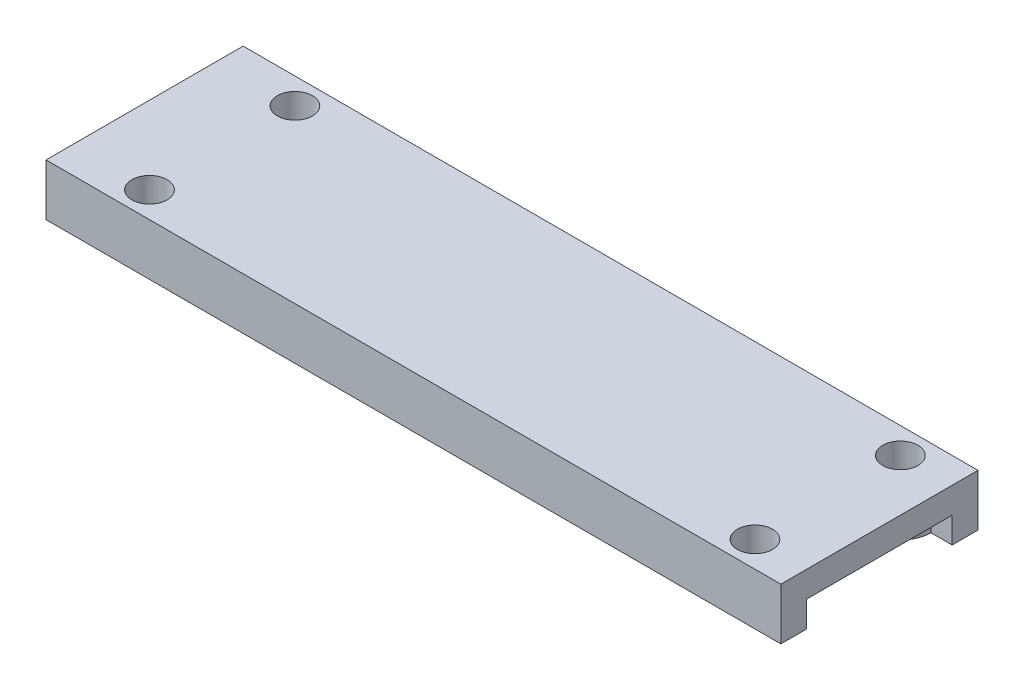
SolidWorks part; units mm, degrees
material "1060 Alloy"
ref_plane "Front Plane" through (0, 0, 0) normal (0, 0, 1) x (1, 0, 0)
ref_plane "Top Plane" through (0, 0, 0) normal (0, 1, 0) x (1, 0, 0)
ref_plane "Right Plane" through (0, 0, 0) normal (1, 0, 0) x (0, 0, -1)
sketch "Sketch1" plane through (0, 0, 0) normal (0, 1, 0) x (1, 0, 0)
  line L1 (-71, -19.05) -> (71, -19.05)
  line L2 (-71, -19.05) -> (-71, 19.05)
  line L3 (-71, 19.05) -> (71, 19.05)
  line L4 (71, -19.05) -> (71, 19.05)
  line L5 (-71, -19.05) -> (71, 19.05) construction
  line L6 (-71, 19.05) -> (71, -19.05) construction
  point P0 (0, 0)
  dimension "D1" = 142
  dimension "D2" = 38.1
extrude "Boss-Extrude1" add sketch "Sketch1" along normal mid plane 10
sketch "Sketch2" plane through (0, 0, 0) normal (1, 0, 0) x (0, 0, -1)
  line L0 (-14.05, 0) -> (14.05, 0)
  line L1 (14.05, 0) -> (14.05, -5)
  line L2 (-19.05, -5) -> (19.05, -5) construction
  line L3 (14.05, -5) -> (-14.05, -5)
  line L4 (-14.05, -5) -> (-14.05, 0)
  line L5 (-19.05, 5) -> (-19.05, -5) construction
  dimension "D1" = 5
extrude "Cut-Extrude1" cut sketch "Sketch2" against normal through all both and the other way through all
hole_wizard "Tap Drill for M8x1.25 Tap1" positions "Sketch4" profile "Sketch3" hole size "M8x1.25" standard "ANSI Metric"
sketch "Sketch4" plane through (0, 5, 0) normal (0, 1, 0) x (1, 0, 0)
  line L0 (71, 19.05) -> (-71, 19.05) construction
  line L2 (-71, 19.05) -> (-71, -19.05) construction
  line L3 (-71, -19.05) -> (71, -19.05) construction
  line L4 (71, -19.05) -> (71, 19.05) construction
  point P0 (-56, 14.05)
  point P2 (61, 14.05)
  point P4 (61, -14.05)
  point P6 (-56, -14.05)
  dimension "D1" = 5
  dimension "D2" = 15
  dimension "D3" = 15
  dimension "D4" = 5
  dimension "D5" = 10
  dimension "D6" = 10
  dimension "D7" = 5
  dimension "D8" = 5
sketch "Sketch3" plane through (-56, 5, -14.05) normal (1, 0, 0) x (0, 0, 1)
  line L0 (0, 0) -> (0, 14.0429)
  line L1 (0, 14.0429) -> (3.4, 12)
  line L2 (3.4, 12) -> (3.4, 0)
  line L5 (3.4, 0) -> (0, 0)
  line L10 (0, 14.0429) -> (-3.4, 12) construction
  line L11 (0, -6.35) -> (0, 107.95) construction
  dimension "Hole Dia." = 6.8
  dimension "Hole Depth" = 12
  dimension "Drill Angle" = 118
cosmetic thread "Cosmetic Thread1" parameters "D2"=8
cosmetic thread "Cosmetic Thread2" parameters "D2"=8
cosmetic thread "Cosmetic Thread3" parameters "D2"=8
cosmetic thread "Cosmetic Thread4" parameters "D2"=8
sketch "Sketch5" plane through (0, 0, 0) normal (0, -1, 0) x (1, 0, 0)
  line L0 (-71, 14.05) -> (-59.4, 14.05) construction
  line L1 (55.1, -14.05) -> (57.6, -14.05)
  line L2 (-52.6, 14.05) -> (-50.1, 14.05)
  line L3 (57.6, -14.05) -> (57.5688, -13.9882)
  line L4 (64.4, -14.05) -> (66.9, -14.05)
  line L5 (55.1, 14.05) -> (57.6, 14.05)
  line L6 (64.4, 14.05) -> (66.9, 14.05)
  line L7 (64.4, -14.05) -> (66.9, -14.05)
  line L8 (64.4, 14.05) -> (66.9, 14.05)
  line L9 (-61.9, 14.05) -> (-59.4, 14.05)
  line L10 (-52.6, 14.05) -> (-50.1, 14.05)
  line L11 (-61.9, -14.05) -> (-59.4, -14.05)
  line L12 (-59.4, -14.05) -> (-59.4026, -14.126)
  line L13 (-52.6, -14.05) -> (-50.1, -14.05)
  arc A0 (-59.4, 14.05) -> (-52.6, 14.05) centre (-56, 14.05) ccw
  arc A1 (-52.6, 14.05) -> (-59.4, 14.05) centre (-56, 14.05) ccw construction
  arc A2 (-61.9, 14.05) -> (-50.1, 14.05) centre (-56, 14.05) ccw
  arc A3 (-59.4, -14.05) -> (-52.6, -14.05) centre (-56, -14.05) cw
  arc A4 (-50.1, -14.05) -> (-61.9, -14.05) centre (-56, -14.05) ccw
  arc A5 (57.6, -14.05) -> (64.4, -14.05) centre (61, -14.05) cw
  arc A6 (66.9, -14.05) -> (55.1, -14.05) centre (61, -14.05) ccw
  arc A7 (57.6, 14.05) -> (64.4, 14.05) centre (61, 14.05) ccw
  arc A8 (55.1, 14.05) -> (66.9, 14.05) centre (61, 14.05) ccw
  line M1 (-71, -14.05) -> (-59.4, -14.05)
  arc M2 (-59.4, -14.05) -> (-52.6, -14.05) centre (-56, -14.05) cw
  line M3 (-52.6, -14.05) -> (57.6, -14.05)
  arc M4 (57.6, -14.05) -> (64.4, -14.05) centre (61, -14.05) cw
  line M5 (64.4, -14.05) -> (71, -14.05)
  line M7 (71, 14.05) -> (64.4, 14.05)
  arc M8 (64.4, 14.05) -> (57.6, 14.05) centre (61, 14.05) cw
  line M9 (57.6, 14.05) -> (-52.6, 14.05)
  arc M10 (-52.6, 14.05) -> (-59.4, 14.05) centre (-56, 14.05) cw
  line M11 (-59.4, 14.05) -> (-71, 14.05)
  dimension "D1" = 3.4
  dimension "D2" = 2.5
  dimension "D3" = 3.4
  dimension "D4" = 2.5
  dimension "D5" = 3.4
  dimension "D6" = 2.5
  dimension "D7" = 3.4
  dimension "D8" = 2.5
extrude "Boss-Extrude2" add sketch "Sketch5" along normal up to surface (5 mm away) contours A4 M3 M1 M2 | A2 M11 M9 M10 | A8 M9 M7 M8 | A6 M5 M3 M4 region at (61, 0, -8.2819) region at (-51.35, 0, -13.9181) region at (56.35, 0, 13.9181) region at (-51.35, 0, 13.9181) up to face at (1.25, -5, 16.15)
